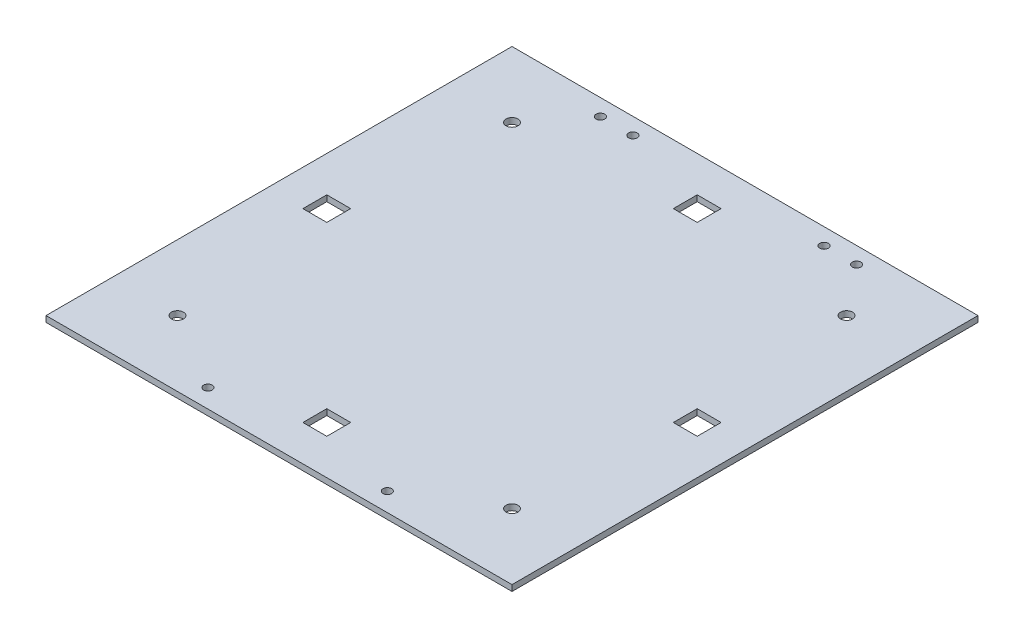
SolidWorks part; units mm, degrees
ref_plane "Front Plane" through (0, 0, 0) normal (0, 0, 1) x (1, 0, 0)
ref_plane "Top Plane" through (0, 0, 0) normal (0, 1, 0) x (1, 0, 0)
ref_plane "Right Plane" through (0, 0, 0) normal (1, 0, 0) x (0, 0, -1)
sketch "Sketch1" plane through (0, 0, 0) normal (0, 1, 0) x (1, 0, 0)
  line L1 (0, 0) -> (247.65, 0)
  line L2 (0, 0) -> (0, 247.65)
  line L3 (0, 247.65) -> (247.65, 247.65)
  line L4 (247.65, 0) -> (247.65, 247.65)
  dimension "D1" = 247.65
  dimension "D2" = 247.65
extrude "Main Body" add sketch "Sketch1" along normal blind 3.175
sketch "Sketch2" plane through (0, 3.175, 0) normal (0, 1, 0) x (1, 0, 0)
  line L0 (58.039, 238.8616) -> (70.739, 238.8616) construction
  line L1 (176.911, 238.8616) -> (189.611, 238.8616) construction
  line L2 (247.65, 247.65) -> (0, 247.65) construction
  line L3 (0, 0) -> (247.65, 0) construction
  line L4 (0, 247.65) -> (0, 0) construction
  line L5 (247.65, 0) -> (247.65, 247.65) construction
  circle A0 centre (55.753, 238.8616) radius 2.286
  circle A1 centre (73.025, 238.8616) radius 2.286
  circle A2 centre (174.625, 238.8616) radius 2.286
  circle A3 centre (191.897, 238.8616) radius 2.286
  circle A4 centre (76.1568, 9.906) radius 2.286
  circle A5 centre (171.4932, 9.906) radius 2.286
  point P14 (123.825, 247.65)
  dimension "D3" = 4.572
  dimension "D7" = 4.572
  dimension "D10" = 76.1568
  dimension "D1" = 12.7
  dimension "D2" = 12.7
  dimension "D4" = 8.7884
  dimension "D5" = 50.8
  dimension "D6" = 50.8
  dimension "D8" = 9.906
  dimension "D9" = 76.1568
extrude "Hinges/Lock Holes" cut sketch "Sketch2" against normal through all
sketch "Sketch3" plane through (0, 3.175, 0) normal (0, 1, 0) x (1, 0, 0)
  line L0 (247.65, 0) -> (0, 247.65) construction
  line L1 (247.65, 247.65) -> (0, 247.65) construction
  line L2 (247.65, 0) -> (247.65, 247.65) construction
  circle A0 centre (212.725, 212.725) radius 3.175
  circle A1 centre (212.725, 34.925) radius 3.175
  circle A2 centre (34.925, 34.925) radius 3.175
  circle A3 centre (34.925, 212.725) radius 3.175
  point P10 (123.825, 123.825)
  dimension "D1" = 6.35
  dimension "D2" = 34.925
  dimension "D3" = 34.925
  dimension "D5" = 177.8
  dimension "D6" = 125.7236
  dimension "D4" = 4
extrude "Thread Holes" cut sketch "Sketch3" against normal through all
sketch "Sketch4" plane through (0, 3.175, 0) normal (0, 1, 0) x (1, 0, 0)
  line L0 (0, 0) -> (247.65, 247.65) construction
  line L1 (117.475, 31.75) -> (130.175, 31.75)
  line L2 (117.475, 31.75) -> (117.475, 19.05)
  line L3 (117.475, 19.05) -> (130.175, 19.05)
  line L4 (130.175, 31.75) -> (130.175, 19.05)
  line L5 (0, 0) -> (247.65, 0) construction
  line L6 (31.75, 130.175) -> (19.05, 130.175)
  line L7 (31.75, 130.175) -> (31.75, 117.475)
  line L8 (31.75, 117.475) -> (19.05, 117.475)
  line L9 (19.05, 130.175) -> (19.05, 117.475)
  line L10 (130.175, 215.9) -> (130.175, 228.6)
  line L11 (130.175, 215.9) -> (117.475, 215.9)
  line L12 (117.475, 215.9) -> (117.475, 228.6)
  line L13 (130.175, 228.6) -> (117.475, 228.6)
  line L14 (215.9, 117.475) -> (228.6, 117.475)
  line L15 (215.9, 117.475) -> (215.9, 130.175)
  line L16 (215.9, 130.175) -> (228.6, 130.175)
  line L17 (228.6, 117.475) -> (228.6, 130.175)
  line L18 (0, 247.65) -> (0, 0) construction
  point P8 (123.825, 123.825)
  point P9 (123.825, 19.05)
  point P12 (123.825, 0)
  point P15 (19.05, 123.825)
  point P28 (0, 123.825)
  dimension "D1" = 12.7
  dimension "D2" = 12.7
  dimension "D3" = 19.05
  dimension "D5" = 19.05
  dimension "D4" = 4
extrude "LED Holes" cut sketch "Sketch4" against normal through all
